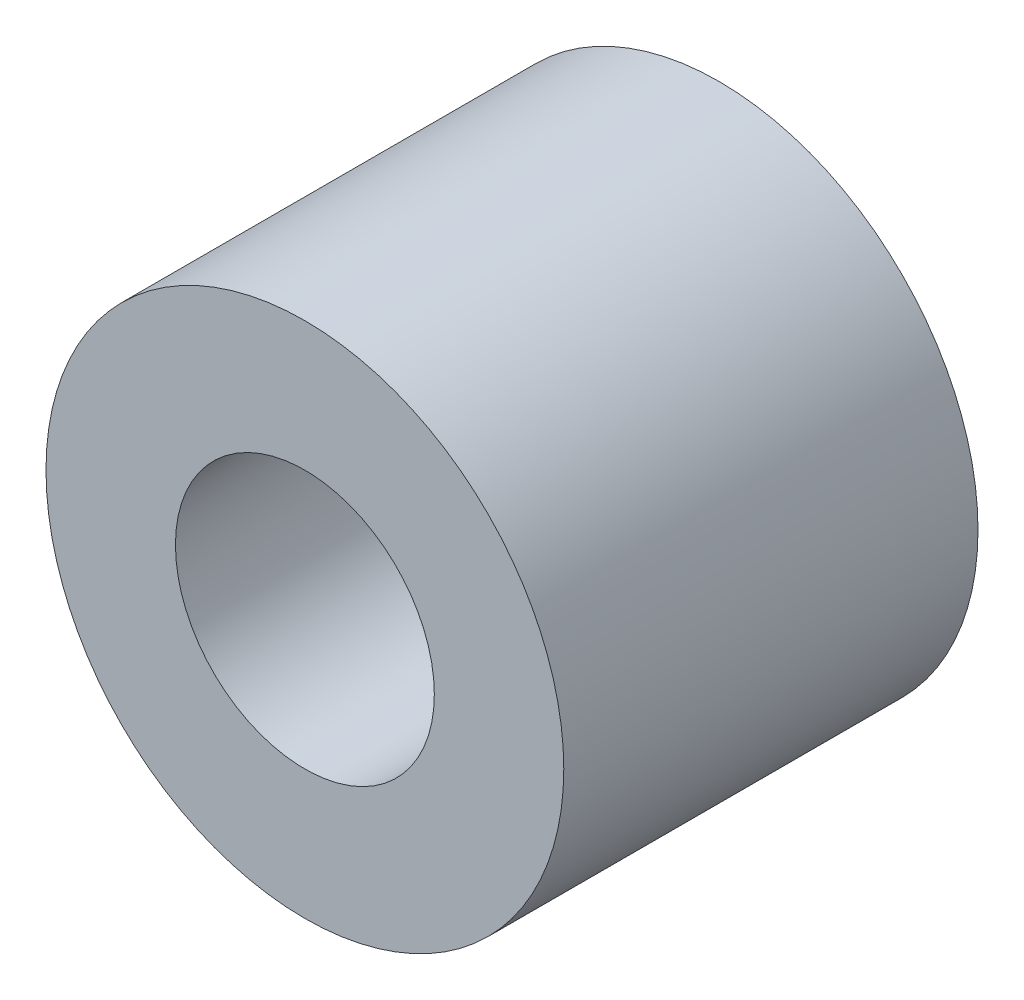
SolidWorks part; units mm, degrees
ref_plane "Front Plane" through (0, 0, 0) normal (0, 0, 1) x (1, 0, 0)
ref_plane "Top Plane" through (0, 0, 0) normal (0, 1, 0) x (1, 0, 0)
ref_plane "Right Plane" through (0, 0, 0) normal (1, 0, 0) x (0, 0, -1)
sketch "Sketch1" plane through (0, 0, 0) normal (1, 0, 0) x (0, 0, -1)
  line L0 (0, 985.393) -> (184.15, 985.393) construction
  line L1 (127, 1017.143) -> (101.6, 1017.143) construction
  line L6 (107.95, 1001.268) -> (158.75, 1001.268)
  line L7 (107.95, 1001.268) -> (107.95, 1017.143)
  line L8 (107.95, 1017.143) -> (158.75, 1017.143)
  line L9 (158.75, 1001.268) -> (158.75, 1017.143)
  line L10 (107.95, 1001.268) -> (184.15, 1001.268) construction
  line L11 (184.15, 1001.268) -> (184.15, 969.518) construction
  point P20 (158.75, 1009.2055)
  dimension "D1" = 25.4
revolve "Revolve1" add sketch "Sketch1" angle 360 about L0
